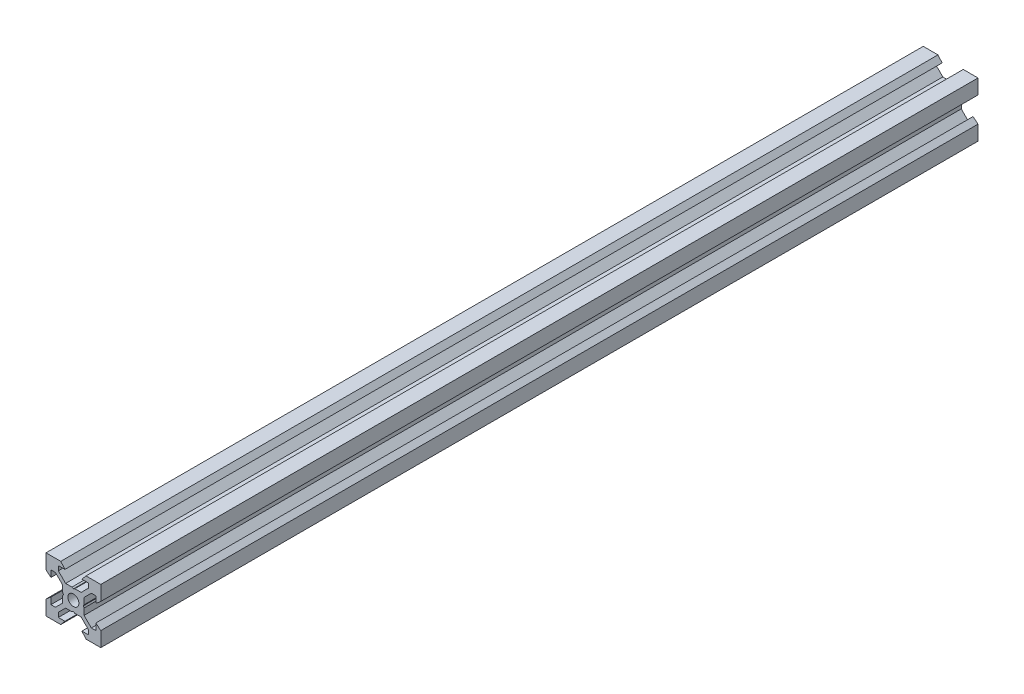
SolidWorks part; units mm, degrees
ref_plane "Front Plane" through (0, 0, 0) normal (0, 0, 1) x (1, 0, 0)
ref_plane "Top Plane" through (0, 0, 0) normal (0, 1, 0) x (1, 0, 0)
ref_plane "Right Plane" through (0, 0, 0) normal (1, 0, 0) x (0, 0, -1)
sketch "Sketch1" plane through (0, 0, 0) normal (0, 0, 1) x (1, 0, 0)
  line L0 (10, 10) -> (4.6104, 10) construction
  line L1 (10, 10) -> (10, 4.6104) construction
  line L2 (10, -10) -> (10, -4.6104) construction
  line L3 (10, -10) -> (4.6104, -10) construction
  line L4 (10, 10) -> (10, 4.6104)
  line L5 (6.5607, 5.5) -> (8.2, 5.5)
  line L6 (5.5, 8.2) -> (5.5, 6.5607)
  line L7 (10, 10) -> (4.6104, 10)
  line L8 (10, 10) -> (10, 4.6104)
  line L9 (6.5607, 5.5) -> (3.9, 2.8393)
  line L10 (5.5, 6.5607) -> (2.8393, 3.9)
  line L11 (10, 4.6104) -> (8.2, 3.1)
  line L12 (4.6104, 10) -> (3.1, 8.2)
  line L13 (8.2, 3.1) -> (8.2, 5.5)
  line L14 (3.1, 8.2) -> (5.5, 8.2)
  line L15 (-6.5607, 5.5) -> (-8.2, 5.5)
  line L16 (6.5607, -5.5) -> (8.2, -5.5)
  line L17 (3.1, -8.2) -> (5.5, -8.2)
  line L18 (8.2, -3.1) -> (8.2, -5.5)
  line L19 (4.6104, -10) -> (3.1, -8.2)
  line L20 (10, -4.6104) -> (8.2, -3.1)
  line L21 (0.5196, -3.9) -> (0, -3.6)
  line L22 (0.5196, 3.9) -> (0, 3.6)
  line L23 (3.6, 0) -> (3.9, -0.5196)
  line L24 (3.9, 0.5196) -> (3.6, 0)
  line L25 (3.9, 0.5196) -> (3.9, 2.8393)
  line L26 (2.8393, 3.9) -> (0.5196, 3.9)
  line L27 (3.9, -2.8393) -> (3.9, -0.5196)
  line L28 (2.8393, -3.9) -> (0.5196, -3.9)
  line L29 (5.5, -6.5607) -> (2.8393, -3.9)
  line L30 (6.5607, -5.5) -> (3.9, -2.8393)
  line L31 (10, -10) -> (10, -4.6104)
  line L32 (10, -10) -> (4.6104, -10)
  line L33 (5.5, -8.2) -> (5.5, -6.5607)
  line L34 (-6.5607, -5.5) -> (-8.2, -5.5)
  line L35 (10, -10) -> (10, -4.6104)
  line L36 (0, 0) -> (0, 8.2) construction
  line L37 (-10, -10) -> (-4.6104, -10) construction
  line L38 (-10, -10) -> (-10, -4.6104) construction
  line L39 (-10, 10) -> (-10, 4.6104) construction
  line L40 (-10, 10) -> (-4.6104, 10) construction
  line L41 (-10, -10) -> (-10, -4.6104)
  line L43 (-5.5, -8.2) -> (-5.5, -6.5607)
  line L44 (-10, -10) -> (-4.6104, -10)
  line L45 (-10, -10) -> (-10, -4.6104)
  line L46 (-6.5607, -5.5) -> (-3.9, -2.8393)
  line L47 (-5.5, -6.5607) -> (-2.8393, -3.9)
  line L48 (-2.8393, -3.9) -> (-0.5196, -3.9)
  line L49 (-3.9, -2.8393) -> (-3.9, -0.5196)
  line L50 (-2.8393, 3.9) -> (-0.5196, 3.9)
  line L51 (-3.9, 0.5196) -> (-3.9, 2.8393)
  line L52 (-3.9, 0.5196) -> (-3.6, 0)
  line L53 (-3.6, 0) -> (-3.9, -0.5196)
  line L54 (-0.5196, 3.9) -> (0, 3.6)
  line L55 (-0.5196, -3.9) -> (0, -3.6)
  line L56 (-10, -4.6104) -> (-8.2, -3.1)
  line L57 (-4.6104, -10) -> (-3.1, -8.2)
  line L58 (-8.2, -3.1) -> (-8.2, -5.5)
  line L59 (-3.1, -8.2) -> (-5.5, -8.2)
  line L60 (-10, -10) -> (10, -10) construction
  line L61 (-10, -10) -> (-10, 10) construction
  line L62 (-3.1, 8.2) -> (-5.5, 8.2)
  line L63 (-8.2, 3.1) -> (-8.2, 5.5)
  line L64 (-4.6104, 10) -> (-3.1, 8.2)
  line L65 (-10, 4.6104) -> (-8.2, 3.1)
  line L66 (-5.5, 6.5607) -> (-2.8393, 3.9)
  line L67 (-6.5607, 5.5) -> (-3.9, 2.8393)
  line L68 (-10, 10) -> (-10, 4.6104)
  line L69 (-10, 10) -> (-4.6104, 10)
  line L70 (-5.5, 8.2) -> (-5.5, 6.5607)
  line L71 (-10, 10) -> (10, 10) construction
  line L72 (-10, 10) -> (-10, 4.6104)
  line L73 (10, -10) -> (10, 10) construction
  line L74 (-10, -10) -> (10, 10) construction
  line L75 (-10, 10) -> (10, -10) construction
  circle A0 centre (0, 0) radius 2
  dimension "D7" = 4
  dimension "D1" = 20
  dimension "D2" = 5.3896
  dimension "D3" = 4.5
  dimension "D4" = 50
  dimension "D5" = 1.8
  dimension "D6" = 1.5104
  dimension "D8" = 5.5
  dimension "D9" = 120
  dimension "D10" = 0.3
  dimension "D11" = 2.3197
  dimension "D12" = 7.8
  dimension "D13" = 7.8
  dimension "D14" = 1.5
  dimension "D15" = 2.6607
extrude "Boss-Extrude1" add sketch "Sketch1" along normal mid plane 320.33 contours L70 L62 L64 L69 L68 L65 L63 L15 L67 L51 L52 L53 L49 L46 L34 L58 L56 L41 L44 L57 L59 L43 L47 L48 L55 L21 L28 L29 L33 L17 L19 L32 L31 L20 L18 L16 L30 L27 L23 L24 L25 L9 L5 L13 L11 L4 L7 L12 L14 L6 L10 region at (9.7172, 7.3052, 0)
